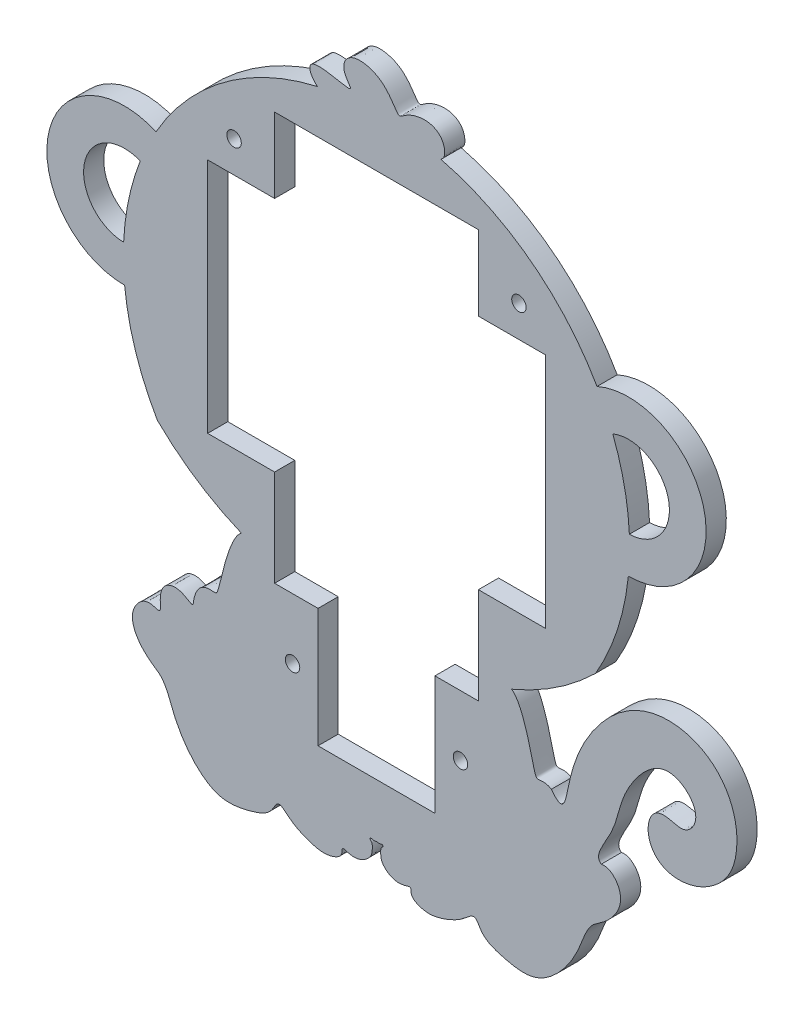
SolidWorks part; units mm, degrees
ref_plane "Front Plane" through (0, 0, 0) normal (0, 0, 1) x (1, 0, 0)
ref_plane "Top Plane" through (0, 0, 0) normal (0, 1, 0) x (1, 0, 0)
ref_plane "Right Plane" through (0, 0, 0) normal (1, 0, 0) x (0, 0, -1)
sketch "Model" plane through (0, 0, 0) normal (0, 0, 1) x (1, 0, 0)
  line L0 (-354.7776, 349.4226) -> (-354.7776, 392.0292) construction
  line L1 (-368.5276, 390.0292) -> (-368.5276, 362.0292)
  line L2 (-368.5276, 390.0292) -> (-341.0276, 390.0292)
  line L21 (-354.7776, 390.0292) -> (-354.7776, 362.0292)
  line L26 (-368.5276, 362.0292) -> (-341.0276, 362.0292)
  line L27 (-341.0276, 390.0292) -> (-341.0276, 362.0292)
  line L28 (-354.7776, 390.0292) -> (-354.7776, 497.7106) construction
  line L29 (-368.5276, 390.0292) -> (-378.7446, 390.0292)
  line L31 (-368.5276, 486.0185) -> (-378.7446, 486.0185)
  line L32 (-378.7446, 390.0292) -> (-378.7446, 486.0185)
  line L33 (-378.7446, 412.6938) -> (-394.4933, 412.6938)
  line L34 (-378.7446, 412.6938) -> (-378.7446, 468.4071)
  line L35 (-378.7446, 468.4071) -> (-394.4933, 468.4071)
  line L36 (-394.4933, 412.6938) -> (-394.4933, 468.4071)
  line L37 (-354.7776, 390.0292) -> (-368.5276, 390.0292)
  line L38 (-354.7776, 390.0292) -> (-354.7776, 486.0185)
  line L39 (-354.7776, 486.0185) -> (-368.5276, 486.0185)
  line L41 (-354.7776, 486.0185) -> (-341.0276, 486.0185)
  line L42 (-341.0276, 486.0185) -> (-330.8106, 486.0185)
  line L43 (-341.0276, 390.0292) -> (-330.8106, 390.0292)
  line L44 (-330.8106, 412.6938) -> (-315.0619, 412.6938)
  line L45 (-315.0619, 412.6938) -> (-315.0619, 468.4071)
  line L46 (-330.8106, 468.4071) -> (-315.0619, 468.4071)
  line L47 (-330.8106, 390.0292) -> (-330.8106, 486.0185)
  circle A0 centre (-295.506, 451.3512) radius 18.2563
  circle A1 centre (-295.506, 451.3512) radius 9.6191
  circle A2 centre (-414.0491, 451.3512) radius 9.6191
  circle A3 centre (-414.0491, 451.3512) radius 18.2562
  arc A4 (-354.7776, 392.0292) -> (-303.2483, 409.4214) centre (-346.9752, 453.9435) ccw
  arc A5 (-303.2483, 409.4214) -> (-354.7776, 497.7106) centre (-353.9365, 439.0196) ccw
  arc A6 (-354.7776, 497.7106) -> (-406.3069, 409.4214) centre (-355.6187, 439.0196) ccw
  arc A7 (-406.3069, 409.4214) -> (-354.7776, 392.0292) centre (-362.58, 453.9435) ccw
  circle A8 centre (-388.2776, 475.7792) radius 1.7 construction
  circle A9 centre (-321.2776, 475.7792) radius 1.7 construction
  circle A10 centre (-388.2776, 475.7792) radius 1.7
  circle A11 centre (-321.2776, 475.7792) radius 1.7
  circle A12 centre (-374.5276, 375.7792) radius 1.7 construction
  circle A13 centre (-335.0276, 375.7792) radius 1.7 construction
  circle A14 centre (-374.5276, 375.7792) radius 1.7
  circle A15 centre (-335.0276, 375.7792) radius 1.7
  spline S0 degree 5 poles (-386.5513, 396.3273) (-386.9161, 396.0792) (-387.366, 395.6344) (-387.8968, 394.8986) (-388.5033, 393.7572) (-389.1715, 392.131) (-389.5779, 391.0147) (-389.9703, 389.8193) (-390.4193, 388.3234) (-390.8333, 386.8049) (-391.2016, 385.3464) (-391.5167, 384.0353) (-391.7817, 382.9443) (-391.9754, 382.2094) (-392.154, 381.6648) (-392.3367, 381.3111) (-392.5515, 381.1299) (-392.8335, 381.0822) (-393.2115, 381.1155) (-393.6934, 381.1695) (-394.2612, 381.1826) (-394.881, 381.0994) (-395.5104, 380.8776) (-396.1059, 380.4945) (-396.6315, 379.9559) (-397.064, 379.2975) (-397.3921, 378.574) (-397.6173, 377.8496) (-397.7535, 377.1888) (-397.8274, 376.647) (-397.8791, 376.2603) (-397.9596, 376.0385) (-398.1148, 375.9725) (-398.366, 376.0408) (-398.7069, 376.2147) (-399.1201, 376.4601) (-399.5915, 376.7412) (-400.118, 377.0223) (-400.6998, 377.2689) (-401.4638, 377.484) (-402.3002, 377.5538) (-403.1741, 377.4267) (-404.0022, 377.0659) (-404.6982, 376.4644) (-405.1535, 375.8118) (-405.4613, 375.0322) (-405.6199, 374.1669) (-405.658, 373.2789) (-405.6265, 372.4425) (-405.5875, 371.7311) (-405.6037, 371.2053) (-405.7274, 370.9008) (-405.9901, 370.8167) (-406.3911, 370.9021) (-406.9056, 371.0748) (-407.4962, 371.2433) (-408.1222, 371.3275) (-408.7511, 371.2827) (-409.3596, 371.0975) (-409.9312, 370.7828) (-410.4544, 370.3635) (-410.9212, 369.8697) (-411.3251, 369.3269) (-411.6596, 368.7503) (-411.9191, 368.1478) (-412.0987, 367.5224) (-412.1944, 366.8744) (-412.2033, 366.204) (-412.0922, 365.2374) (-411.7958, 364.2405) (-411.2536, 363.0979) (-410.5055, 362.004) (-409.6286, 361.0209) (-408.9407, 360.363) (-408.2617, 359.7955) (-407.7193, 359.3836) (-407.2138, 359.0282) (-406.7532, 358.7179) (-406.3372, 358.4326) (-405.9584, 358.1461) (-405.6064, 357.8322) (-405.2709, 357.469) (-404.9452, 357.0452) (-404.6288, 356.5637) (-404.3252, 356.0366) (-404.0394, 355.4808) (-403.7755, 354.9137) (-403.4863, 354.2349) (-403.2244, 353.5638) (-402.972, 352.8931) (-402.7045, 352.203) (-402.4017, 351.478) (-402.0626, 350.7211) (-401.6746, 349.928) (-401.239, 349.111) (-400.7631, 348.2898) (-400.2543, 347.482) (-399.7226, 346.693) (-399.1634, 345.9321) (-398.5743, 345.1992) (-397.9495, 344.4888) (-397.2819, 343.7971) (-396.6937, 343.2329) (-395.9467, 342.5739) (-395.1459, 341.9478) (-394.2909, 341.3752) (-393.3842, 340.8821) (-392.43, 340.4917) (-391.606, 340.244) (-390.756, 340.0794) (-389.8831, 339.9983) (-388.9906, 339.995) (-388.0822, 340.0607) (-387.1626, 340.184) (-386.2377, 340.3533) (-385.315, 340.5579) (-384.404, 340.7898) (-383.5163, 341.0454) (-382.6665, 341.327) (-381.8713, 341.6429) (-381.1468, 342.0028) (-380.5061, 342.4143) (-379.9577, 342.8796) (-379.5022, 343.3918) (-379.1308, 343.9312) (-378.8219, 344.461) (-378.5447, 344.9321) (-378.2678, 345.2959) (-377.9655, 345.5144) (-377.6259, 345.571) (-377.2571, 345.4813) (-376.8758, 345.2788) (-376.4963, 345.0025) (-376.1171, 344.6823) (-375.7208, 344.3352) (-375.2832, 343.9706) (-374.7791, 343.5936) (-374.1903, 343.2075) (-373.3777, 342.7411) (-372.4498, 342.2849) (-371.4489, 341.8618) (-370.4344, 341.4969) (-369.4571, 341.2116) (-368.6859, 341.0352) (-367.9644, 340.9249) (-367.2855, 340.8811) (-366.6359, 340.9021) (-366.0015, 340.9842) (-365.3739, 341.1239) (-364.7563, 341.3185) (-364.1709, 341.5681) (-363.6579, 341.8743) (-363.2584, 342.2351) (-362.9996, 342.6398) (-362.8828, 343.0653) (-362.8624, 343.4679) (-362.8603, 343.7943) (-362.8008, 344.002) (-362.6453, 344.0822) (-362.4039, 344.0645) (-362.091, 343.9838) (-361.7122, 343.8689) (-361.2711, 343.747) (-360.7722, 343.6434) (-360.2251, 343.5846) (-359.6439, 343.594) (-359.0456, 343.6889) (-358.3311, 343.9146) (-357.653, 344.2718) (-357.0557, 344.716) (-356.5775, 345.1787) (-356.2334, 345.621) (-356.0331, 345.9754) (-355.9027, 346.3429) (-355.8208, 346.7573) (-355.7698, 347.2366) (-355.7451, 347.7596) (-355.7624, 348.2488) (-355.8386, 348.6234) (-355.9777, 348.8376) (-356.1508, 348.9418) (-356.2927, 349.0757) (-356.3365, 349.2881) (-356.2363, 349.4431) (-355.9971, 349.4554) (-355.6775, 349.3823) (-355.3456, 349.3188) (-355.1001, 349.3199) (-354.9324, 349.357) (-354.828, 349.398) (-354.7776, 349.4226) knots 0 0 0 0 0 0 0.02 0.025 0.03 0.035 0.04 0.045 0.05 0.06 0.065 0.07 0.075 0.08 0.085 0.09 0.095 0.1 0.105 0.11 0.115 0.12 0.125 0.13 0.135 0.14 0.145 0.15 0.155 0.16 0.165 0.17 0.175 0.18 0.185 0.19 0.195 0.2 0.205 0.21 0.22 0.225 0.23 0.235 0.24 0.245 0.25 0.255 0.26 0.265 0.27 0.275 0.28 0.285 0.29 0.295 0.3 0.305 0.31 0.315 0.32 0.325 0.33 0.335 0.34 0.345 0.35 0.355 0.36 0.375 0.38 0.39 0.395 0.4 0.405 0.41 0.415 0.42 0.425 0.43 0.435 0.44 0.445 0.45 0.455 0.46 0.465 0.47 0.48 0.485 0.49 0.495 0.5 0.51 0.515 0.52 0.525 0.53 0.54 0.545 0.55 0.555 0.56 0.565 0.575 0.58 0.585 0.59 0.595 0.6 0.605 0.61 0.615 0.62 0.625 0.63 0.635 0.64 0.645 0.65 0.655 0.66 0.665 0.67 0.675 0.68 0.685 0.69 0.695 0.7 0.705 0.71 0.715 0.72 0.725 0.73 0.735 0.74 0.745 0.755 0.76 0.765 0.77 0.775 0.78 0.785 0.79 0.795 0.8 0.805 0.81 0.815 0.82 0.825 0.83 0.835 0.84 0.845 0.85 0.855 0.86 0.865 0.87 0.875 0.88 0.885 0.89 0.895 0.905 0.91 0.915 0.92 0.925 0.93 0.935 0.94 0.945 0.95 0.955 0.96 0.965 0.97 0.975 0.98 0.985 0.99 0.995 1 1 1 1 1 1 weights 1 1 1 1 1 1 1 1 1 1 1 1 1 1 1 1 1 1 1 1 1 1 1 1 1 1 1 1 1 1 1 1 1 1 1 1 1 1 1 1 1 1 1 1 1 1 1 1 1 1 1 1 1 1 1 1 1 1 1 1 1 1 1 1 1 1 1 1 1 1 1 1 1 1 1 1 1 1 1 1 1 1 1 1 1 1 1 1 1 1 1 1 1 1 1 1 1 1 1 1 1 1 1 1 1 1 1 1 1 1 1 1 1 1 1 1 1 1 1 1 1 1 1 1 1 1 1 1 1 1 1 1 1 1 1 1 1 1 1 1 1 1 1 1 1 1 1 1 1 1 1 1 1 1 1 1 1 1 1 1 1 1 1 1 1 1 1 1 1 1 1 1 1 1 1 1 1 1 1 1 1 1 1 1 1 1 1 1 1 1 1
  spline S1 degree 5 poles (-323.0039, 396.3273) (-322.6391, 396.0792) (-322.1892, 395.6344) (-321.6584, 394.8986) (-321.0519, 393.7572) (-320.3837, 392.131) (-319.9773, 391.0147) (-319.5849, 389.8193) (-319.1359, 388.3234) (-318.7219, 386.8049) (-318.3536, 385.3464) (-318.0385, 384.0353) (-317.7735, 382.9443) (-317.5798, 382.2094) (-317.4012, 381.6648) (-317.2185, 381.3111) (-317.0037, 381.1299) (-316.7217, 381.0822) (-316.3437, 381.1155) (-315.8618, 381.1695) (-315.294, 381.1826) (-314.6741, 381.0994) (-314.0448, 380.8776) (-313.4493, 380.4945) (-312.9237, 379.9559) (-312.4912, 379.2975) (-312.1631, 378.574) (-311.9379, 377.8496) (-311.8017, 377.1888) (-311.7278, 376.647) (-311.6761, 376.2603) (-311.5956, 376.0385) (-311.4404, 375.9725) (-311.1892, 376.0408) (-310.8483, 376.2147) (-310.4351, 376.4601) (-309.9637, 376.7412) (-309.4372, 377.0223) (-308.8554, 377.2689) (-308.0914, 377.484) (-307.2549, 377.5538) (-306.3811, 377.4267) (-305.553, 377.0659) (-304.857, 376.4644) (-304.4017, 375.8118) (-304.0939, 375.0322) (-303.9353, 374.1669) (-303.8972, 373.2789) (-303.9287, 372.4425) (-303.9677, 371.7311) (-303.9515, 371.2053) (-303.8278, 370.9008) (-303.5651, 370.8167) (-303.1641, 370.9021) (-302.6496, 371.0748) (-302.0589, 371.2433) (-301.433, 371.3275) (-300.8041, 371.2827) (-300.1956, 371.0975) (-299.624, 370.7828) (-299.1008, 370.3635) (-298.634, 369.8697) (-298.2301, 369.3269) (-297.8956, 368.7503) (-297.6361, 368.1478) (-297.4565, 367.5224) (-297.3608, 366.8744) (-297.3519, 366.204) (-297.463, 365.2374) (-297.7594, 364.2405) (-298.3016, 363.0979) (-299.0496, 362.004) (-299.9266, 361.0209) (-300.6145, 360.363) (-301.2935, 359.7955) (-301.8359, 359.3836) (-302.3414, 359.0282) (-302.8019, 358.7179) (-303.218, 358.4326) (-303.5968, 358.1461) (-303.9488, 357.8322) (-304.2843, 357.469) (-304.61, 357.0452) (-304.9264, 356.5637) (-305.23, 356.0366) (-305.5158, 355.4808) (-305.7797, 354.9137) (-306.0689, 354.2349) (-306.3308, 353.5638) (-306.5832, 352.8931) (-306.8507, 352.203) (-307.1535, 351.478) (-307.4926, 350.7211) (-307.8805, 349.928) (-308.3162, 349.111) (-308.7921, 348.2898) (-309.3008, 347.482) (-309.8326, 346.693) (-310.3918, 345.9321) (-310.9809, 345.1992) (-311.6057, 344.4888) (-312.2733, 343.7971) (-312.8615, 343.2329) (-313.6085, 342.5739) (-314.4093, 341.9478) (-315.2643, 341.3752) (-316.171, 340.8821) (-317.1251, 340.4917) (-317.9492, 340.244) (-318.7992, 340.0794) (-319.6721, 339.9983) (-320.5646, 339.995) (-321.473, 340.0607) (-322.3926, 340.184) (-323.3175, 340.3533) (-324.2402, 340.5579) (-325.1512, 340.7898) (-326.0389, 341.0454) (-326.8887, 341.327) (-327.6839, 341.6429) (-328.4084, 342.0028) (-329.049, 342.4143) (-329.5975, 342.8796) (-330.053, 343.3918) (-330.4244, 343.9312) (-330.7333, 344.461) (-331.0105, 344.9321) (-331.2874, 345.2959) (-331.5897, 345.5144) (-331.9293, 345.571) (-332.298, 345.4813) (-332.6794, 345.2788) (-333.0589, 345.0025) (-333.4381, 344.6823) (-333.8343, 344.3352) (-334.272, 343.9706) (-334.7761, 343.5936) (-335.3649, 343.2075) (-336.1775, 342.7411) (-337.1053, 342.2849) (-338.1063, 341.8618) (-339.1207, 341.4969) (-340.0981, 341.2116) (-340.8693, 341.0352) (-341.5908, 340.9249) (-342.2697, 340.8811) (-342.9193, 340.9021) (-343.5537, 340.9842) (-344.1813, 341.1239) (-344.7989, 341.3185) (-345.3842, 341.5681) (-345.8972, 341.8743) (-346.2968, 342.2351) (-346.5556, 342.6398) (-346.6724, 343.0653) (-346.6928, 343.4679) (-346.6949, 343.7943) (-346.7544, 344.002) (-346.9099, 344.0822) (-347.1513, 344.0645) (-347.4642, 343.9838) (-347.843, 343.8689) (-348.2841, 343.747) (-348.783, 343.6434) (-349.33, 343.5846) (-349.9113, 343.594) (-350.5096, 343.6889) (-351.2241, 343.9146) (-351.9022, 344.2718) (-352.4995, 344.716) (-352.9777, 345.1787) (-353.3218, 345.621) (-353.5221, 345.9754) (-353.6525, 346.3429) (-353.7344, 346.7573) (-353.7854, 347.2366) (-353.8101, 347.7596) (-353.7928, 348.2488) (-353.7166, 348.6234) (-353.5775, 348.8376) (-353.4043, 348.9418) (-353.2625, 349.0757) (-353.2187, 349.2881) (-353.3188, 349.4431) (-353.5581, 349.4554) (-353.8776, 349.3823) (-354.2096, 349.3188) (-354.4551, 349.3199) (-354.6228, 349.357) (-354.7272, 349.398) (-354.7776, 349.4226) knots 0 0 0 0 0 0 0.02 0.025 0.03 0.035 0.04 0.045 0.05 0.06 0.065 0.07 0.075 0.08 0.085 0.09 0.095 0.1 0.105 0.11 0.115 0.12 0.125 0.13 0.135 0.14 0.145 0.15 0.155 0.16 0.165 0.17 0.175 0.18 0.185 0.19 0.195 0.2 0.205 0.21 0.22 0.225 0.23 0.235 0.24 0.245 0.25 0.255 0.26 0.265 0.27 0.275 0.28 0.285 0.29 0.295 0.3 0.305 0.31 0.315 0.32 0.325 0.33 0.335 0.34 0.345 0.35 0.355 0.36 0.375 0.38 0.39 0.395 0.4 0.405 0.41 0.415 0.42 0.425 0.43 0.435 0.44 0.445 0.45 0.455 0.46 0.465 0.47 0.48 0.485 0.49 0.495 0.5 0.51 0.515 0.52 0.525 0.53 0.54 0.545 0.55 0.555 0.56 0.565 0.575 0.58 0.585 0.59 0.595 0.6 0.605 0.61 0.615 0.62 0.625 0.63 0.635 0.64 0.645 0.65 0.655 0.66 0.665 0.67 0.675 0.68 0.685 0.69 0.695 0.7 0.705 0.71 0.715 0.72 0.725 0.73 0.735 0.74 0.745 0.755 0.76 0.765 0.77 0.775 0.78 0.785 0.79 0.795 0.8 0.805 0.81 0.815 0.82 0.825 0.83 0.835 0.84 0.845 0.85 0.855 0.86 0.865 0.87 0.875 0.88 0.885 0.89 0.895 0.905 0.91 0.915 0.92 0.925 0.93 0.935 0.94 0.945 0.95 0.955 0.96 0.965 0.97 0.975 0.98 0.985 0.99 0.995 1 1 1 1 1 1 weights 1 1 1 1 1 1 1 1 1 1 1 1 1 1 1 1 1 1 1 1 1 1 1 1 1 1 1 1 1 1 1 1 1 1 1 1 1 1 1 1 1 1 1 1 1 1 1 1 1 1 1 1 1 1 1 1 1 1 1 1 1 1 1 1 1 1 1 1 1 1 1 1 1 1 1 1 1 1 1 1 1 1 1 1 1 1 1 1 1 1 1 1 1 1 1 1 1 1 1 1 1 1 1 1 1 1 1 1 1 1 1 1 1 1 1 1 1 1 1 1 1 1 1 1 1 1 1 1 1 1 1 1 1 1 1 1 1 1 1 1 1 1 1 1 1 1 1 1 1 1 1 1 1 1 1 1 1 1 1 1 1 1 1 1 1 1 1 1 1 1 1 1 1 1 1 1 1 1 1 1 1 1 1 1 1 1 1 1 1 1 1
  spline S2 degree 5 poles (-313.6608, 380.6036) (-313.4447, 380.3201) (-313.0302, 379.8091) (-312.4617, 379.2104) (-311.8099, 378.7481) (-311.1658, 378.7209) (-310.6734, 379.2168) (-310.2927, 380.1782) (-309.9686, 381.5239) (-309.6406, 383.1622) (-309.2509, 385.0015) (-308.7553, 386.9633) (-308.0017, 389.3938) (-307.0301, 391.8531) (-305.8363, 394.2764) (-304.438, 396.6235) (-302.856, 398.8596) (-301.4232, 400.6299) (-299.5708, 402.6142) (-297.5538, 404.3848) (-295.3743, 405.8881) (-292.6508, 407.2693) (-289.33, 408.2696) (-286.299, 408.5941) (-283.2651, 408.3445) (-280.3791, 407.5391) (-278.0928, 406.4785) (-276.3489, 405.3668) (-274.4851, 403.7878) (-272.9371, 401.946) (-271.7278, 399.9069) (-270.8571, 397.7451) (-270.3065, 395.5388) (-270.0462, 393.71) (-269.965, 391.9301) (-270.041, 390.2346) (-270.2523, 388.6524) (-270.5799, 387.2019) (-271.0097, 385.8888) (-271.5359, 384.701) (-272.1612, 383.6109) (-272.8958, 382.5869) (-273.7555, 381.6014) (-274.7609, 380.6417) (-275.9355, 379.7174) (-277.2973, 378.8569) (-278.8515, 378.1044) (-280.5823, 377.5164) (-282.4459, 377.1586) (-284.3607, 377.1036) (-286.2191, 377.417) (-287.9032, 378.1427) (-289.299, 379.2867) (-290.311, 380.8037) (-290.8776, 382.5789) (-290.9832, 384.4209) (-290.6506, 386.112) (-289.936, 387.4514) (-288.9223, 388.2997) (-287.7148, 388.6275) (-286.4328, 388.5495) (-285.1876, 388.2576) (-284.0619, 387.9667) (-283.0865, 387.8525) (-282.2242, 388) (-281.4248, 388.4326) (-280.673, 389.1343) (-280.0427, 390.0762) (-279.6515, 391.2145) (-279.6146, 392.4895) (-279.9934, 393.8227) (-280.764, 395.118) (-281.8511, 396.2738) (-283.152, 397.1938) (-284.5629, 397.798) (-286.0086, 398.0348) (-287.4505, 397.8849) (-288.8706, 397.3556) (-290.2614, 396.4772) (-291.6143, 395.2987) (-292.9061, 393.8845) (-294.101, 392.3076) (-295.162, 390.6429) (-296.0582, 388.9596) (-296.775, 387.314) (-297.3214, 385.7431) (-297.7428, 384.2552) (-298.1147, 382.8324) (-298.5188, 381.4451) (-299.0233, 380.0639) (-299.6638, 378.6704) (-300.4174, 377.2729) (-301.2032, 375.907) (-301.9108, 374.6227) (-302.4229, 373.4731) (-302.6383, 372.5046) (-302.5279, 371.8953) (-302.2784, 371.535) (-302.0378, 371.3378) (-301.8989, 371.25) knots 0 0 0 0 0 0 0.01 0.02 0.03 0.04 0.05 0.06 0.07 0.08 0.09 0.1 0.11 0.13 0.14 0.15 0.16 0.17 0.18 0.2 0.21 0.22 0.24 0.26 0.27 0.28 0.29 0.3 0.31 0.33 0.34 0.35 0.36 0.37 0.38 0.39 0.4 0.41 0.42 0.43 0.44 0.45 0.46 0.47 0.48 0.49 0.5 0.51 0.52 0.53 0.54 0.55 0.56 0.57 0.58 0.59 0.6 0.61 0.62 0.63 0.64 0.65 0.66 0.67 0.68 0.69 0.7 0.71 0.72 0.73 0.74 0.75 0.76 0.77 0.78 0.79 0.8 0.81 0.82 0.83 0.84 0.85 0.86 0.87 0.88 0.89 0.9 0.91 0.92 0.93 0.94 0.95 0.96 0.97 0.98 0.99 1 1 1 1 1 1 weights 1 1 1 1 1 1 1 1 1 1 1 1 1 1 1 1 1 1 1 1 1 1 1 1 1 1 1 1 1 1 1 1 1 1 1 1 1 1 1 1 1 1 1 1 1 1 1 1 1 1 1 1 1 1 1 1 1 1 1 1 1 1 1 1 1 1 1 1 1 1 1 1 1 1 1 1 1 1 1 1 1 1 1 1 1 1 1 1 1 1 1 1 1 1 1 1 1 1 1 1
  spline S3 degree 5 poles (-368.6485, 496.2522) (-368.7445, 496.3189) (-368.9332, 496.4614) (-369.2068, 496.7025) (-369.5526, 497.079) (-369.9454, 497.6352) (-370.274, 498.2589) (-370.4903, 498.915) (-370.5107, 499.5416) (-370.2384, 500.0643) (-369.5991, 500.4175) (-368.5716, 500.5624) (-367.2236, 500.5088) (-365.6871, 500.3043) (-364.1304, 500.0214) (-362.7304, 499.745) (-361.6458, 499.5606) (-360.9878, 499.5411) (-360.7964, 499.7361) (-361.0037, 500.1558) (-361.4562, 500.7754) (-361.9696, 501.5464) (-362.3683, 502.407) (-362.5408, 503.2925) (-362.4544, 504.1433) (-362.127, 504.907) (-361.609, 505.5429) (-360.9624, 506.0248) (-360.2377, 506.3463) (-359.4651, 506.519) (-358.6621, 506.5638) (-357.8368, 506.5034) (-356.9934, 506.3554) (-356.1367, 506.1232) (-355.2752, 505.7947) (-354.4199, 505.3529) (-353.5839, 504.7839) (-352.7824, 504.0858) (-352.0321, 503.2767) (-351.3511, 502.4053) (-350.7568, 501.5504) (-350.2591, 500.8009) (-349.8549, 500.2405) (-349.5224, 499.9306) (-349.215, 499.8941) (-348.8555, 500.0985) (-348.3621, 500.4755) (-347.6717, 500.9383) (-346.77, 501.4022) (-345.6888, 501.7923) (-344.4899, 502.0451) (-343.2539, 502.1125) (-342.0666, 501.9648) (-341.0067, 501.594) (-340.1326, 501.0174) (-339.4704, 500.2805) (-339.0219, 499.4471) (-338.7725, 498.5899) (-338.6988, 497.7804) (-338.776, 497.0807) (-338.9866, 496.5313) (-339.2553, 496.2274) (-339.5119, 496.0787) (-339.7073, 496.0148) (-339.8111, 495.9917) knots 0 0 0 0 0 0 0.016667 0.033333 0.05 0.066667 0.083333 0.1 0.116667 0.133333 0.15 0.166667 0.183333 0.2 0.216667 0.233333 0.25 0.266667 0.283333 0.3 0.316667 0.333333 0.35 0.366667 0.383333 0.4 0.416667 0.433333 0.45 0.466667 0.483333 0.5 0.516667 0.533333 0.55 0.566667 0.583333 0.6 0.616667 0.633333 0.65 0.666667 0.683333 0.7 0.716667 0.733333 0.75 0.766667 0.783333 0.8 0.816667 0.833333 0.85 0.866667 0.883333 0.9 0.916667 0.933333 0.95 0.966667 0.983333 1 1 1 1 1 1 weights 1 1 1 1 1 1 1 1 1 1 1 1 1 1 1 1 1 1 1 1 1 1 1 1 1 1 1 1 1 1 1 1 1 1 1 1 1 1 1 1 1 1 1 1 1 1 1 1 1 1 1 1 1 1 1 1 1 1 1 1 1 1 1 1 1
  dimension "D2" = 13.75
  dimension "D3" = 2
  dimension "D1" = 28
extrude "Boss-Extrude1" add sketch "Model" along normal blind 4.75 contours A6 A7 A4 A5 A0 A3 | A3 A6 A2 | A2 A6 | A6 A3 A2 | A1 A5 A0 | A1 A5 | A5 A1 A0 | S2 S1 A4 L47 L43 L27 L26 L1 L29 L32 A7 S0 | S2 S1 | S3 A6 A5 region at (-369.8065, 376.0292, 0) region at (-382.1837, 396.3619, 0) region at (-404.0204, 449.2347, 0) region at (-431.4752, 455.029, 0) region at (-305.971, 377.819, 0) region at (-294.8154, 437.3981, 0) region at (-305.5348, 449.2347, 0) region at (-409.3752, 450.3648, 0) region at (-300.18, 450.3648, 0) region at (-354.5371, 500.3437, 0)
